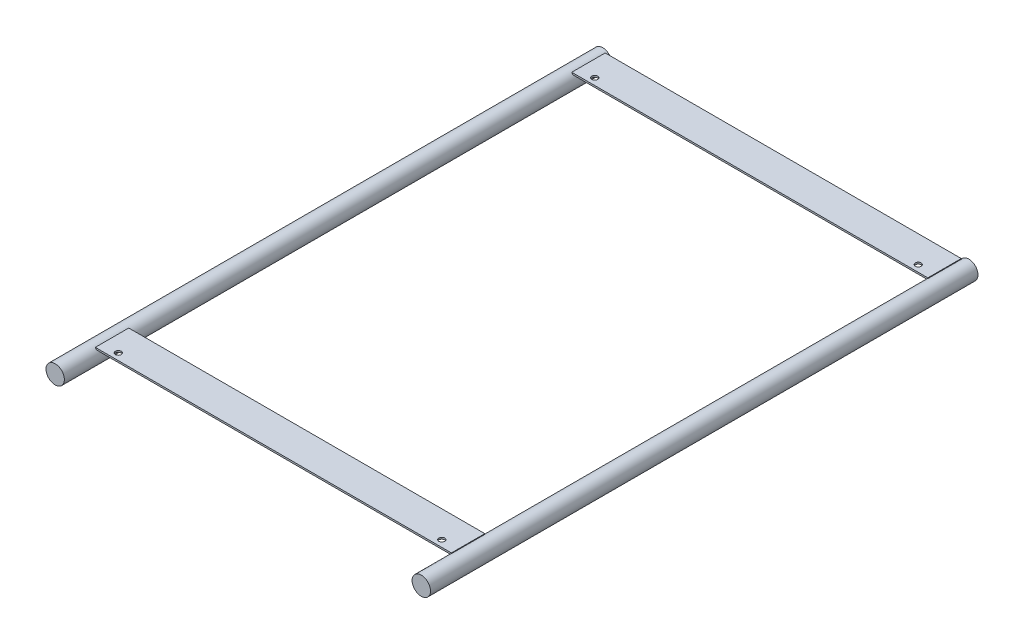
SolidWorks part; units mm, degrees
material "acier chariot"
ref_plane "Front Plane" through (0, 0, 0) normal (0, 0, 1) x (1, 0, 0)
ref_plane "Top Plane" through (0, 0, 0) normal (0, 1, 0) x (1, 0, 0)
ref_plane "Right Plane" through (0, 0, 0) normal (1, 0, 0) x (0, 0, -1)
sketch "Sketch1" plane through (0, 0, 0) normal (0, 0, 1) x (1, 0, 0)
  line L0 (-219, 0) -> (219, 0) construction
  circle A0 centre (-219, 0) radius 11
  circle A1 centre (219, 0) radius 11
  dimension "D1" = 22
  dimension "D2" = 438
extrude "Boss-Extrude1" add sketch "Sketch1" along normal blind 655
ref_plane "Plane1" through (0, 8, 0) normal (0, 1, 0) x (1, 0, 0)
sketch "Sketch2" plane through (0, 8, 0) normal (0, 1, 0) x (1, 0, 0)
  line L0 (0, 96.1826) -> (0, -720.2103) construction
  line L1 (-208, 0) -> (-230, 0) construction
  line L2 (-213, -3) -> (213, -3)
  line L3 (-213, -3) -> (-213, -43)
  line L4 (-213, -43) -> (213, -43)
  line L5 (213, -3) -> (213, -43)
  line L6 (-213, -3) -> (213, -43) construction
  line L7 (-213, -43) -> (213, -3) construction
  point P3 (0, -23)
  dimension "D1" = 3
  dimension "D2" = 40
  dimension "D3" = 426
extrude "Boss-Extrude2" add sketch "Sketch2" along normal blind 2
ref_axis "Axis1" through (-219, 0, 655) along (0, 0, -1)
sketch "Sketch3" plane through (0, 10, 0) normal (0, 1, 0) x (1, 0, 0)
  line L0 (0, 59.031) -> (0, -93.1454) construction
  line L1 (-213, -43) -> (213, -43) construction
  circle A0 centre (-193.5, -35) radius 3.5
  circle A1 centre (193.5, -35) radius 3.5
  dimension "D1" = 7
  dimension "D3" = 387
  dimension "D2" = 8
pattern_linear "LPattern1" count 2 spacing 570 along (0, 0, 1) of "Boss-Extrude2"
extrude "Cut-Extrude1" cut sketch "Sketch3" against normal through all
sketch "Sketch4" plane through (0, 10, 0) normal (0, 1, 0) x (1, 0, 0)
  line L0 (0, -547.2804) -> (0, -663.7075) construction
  line L1 (-213, -613) -> (213, -613) construction
  circle A0 centre (-193.5, -605) radius 3.5
  circle A1 centre (193.5, -605) radius 3.5
  dimension "D1" = 7
  dimension "D3" = 387
  dimension "D2" = 8
extrude "Cut-Extrude2" cut sketch "Sketch4" against normal through all
